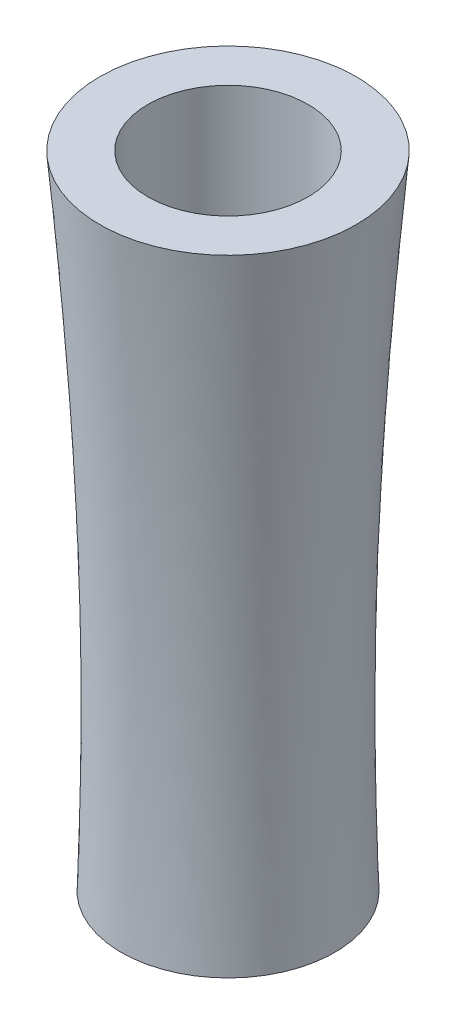
SolidWorks part; units mm, degrees
ref_plane "Front Plane" through (0, 0, 0) normal (0, 0, 1) x (1, 0, 0)
ref_plane "Top Plane" through (0, 0, 0) normal (0, 1, 0) x (1, 0, 0)
ref_plane "Right Plane" through (0, 0, 0) normal (1, 0, 0) x (0, 0, -1)
sketch "Sketch1" plane through (0, 0, 0) normal (0, 1, 0) x (1, 0, 0)
  circle A0 centre (0, 0) radius 10
  dimension "D1" = 20
ref_plane "Plane1" through (0, 60, 0) normal (0, 1, 0) x (1, 0, 0)
sketch "Sketch2" plane through (0, 60, 0) normal (0, 1, 0) x (1, 0, 0)
  circle A0 centre (0, 0) radius 12
  dimension "D1" = 24
loft "Loft1" add profiles "Sketch1", "Sketch2" connector at (6.316, 0, 7.753) connector at (-2.0483, 60, 11.8239)
sketch "Sketch3" plane through (0, 60, 0) normal (0, 1, 0) x (1, 0, 0)
  circle A0 centre (0, 0) radius 7.5
  dimension "D1" = 15
extrude "Cut-Extrude1" cut sketch "Sketch3" against normal through all both and the other way through all
